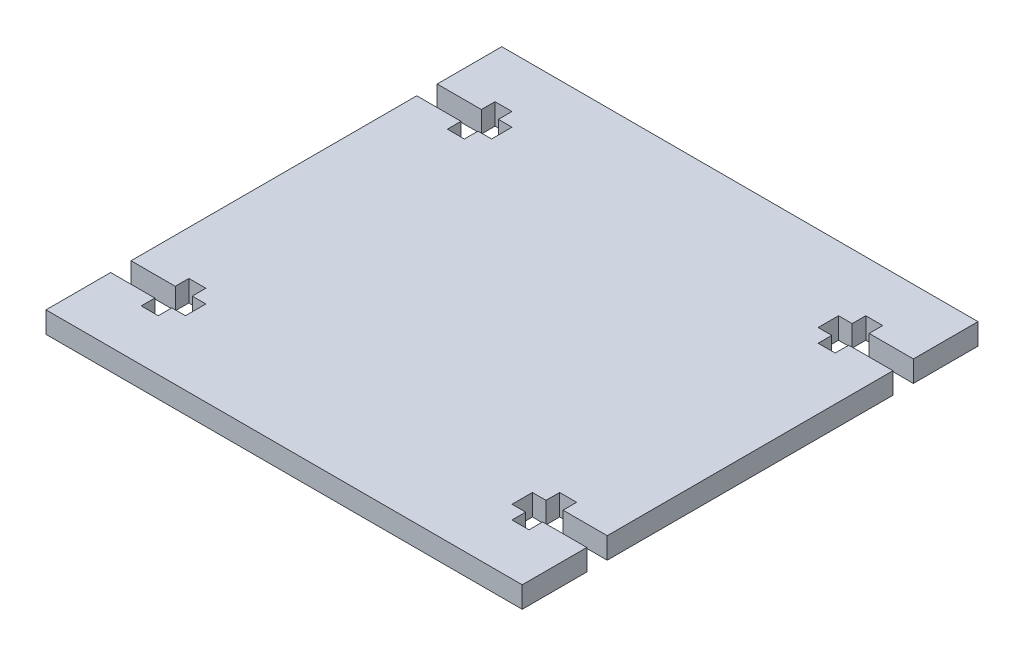
SolidWorks part; units mm, degrees
ref_plane "Front Plane" through (0, 0, 0) normal (0, 0, 1) x (1, 0, 0)
ref_plane "Top Plane" through (0, 0, 0) normal (0, 1, 0) x (1, 0, 0)
ref_plane "Right Plane" through (0, 0, 0) normal (1, 0, 0) x (0, 0, -1)
sketch "Sketch1" plane through (0, 0, 0) normal (0, 1, 0) x (1, 0, 0)
  line L0 (0, 22.5) -> (35, 22.5) construction
  line L1 (0, 33.5) -> (35, 33.5)
  line L2 (0, 33.5) -> (0, 0)
  line L3 (0, 0) -> (35, 0)
  line L4 (35, 33.5) -> (35, 24)
  line L5 (35, 24) -> (28.5, 24)
  line L6 (28.5, 24) -> (28.5, 26)
  line L7 (28.5, 26) -> (26, 26)
  line L8 (26, 26) -> (26, 24)
  line L9 (26, 24) -> (24, 24)
  line L10 (24, 24) -> (24, 21)
  line L11 (24, 21) -> (26, 21)
  line L12 (26, 21) -> (26, 19)
  line L13 (26, 19) -> (28.5, 19)
  line L14 (28.5, 19) -> (28.5, 21)
  line L15 (28.5, 21) -> (35, 21)
  line L16 (35, 21) -> (35, 0)
  point P17 (24, 22.5)
  dimension "D1" = 35
  dimension "D2" = 2.5
  dimension "D3" = 9
  dimension "D4" = 2
  dimension "D5" = 3
  dimension "D6" = 7.5
  dimension "D7" = 7
  dimension "D8" = 22.5
extrude "Boss-Extrude1" add sketch "Sketch1" along normal mid plane 3.125
mirror "Mirror1" about plane through (0, 0, 0) normal (1, 0, 0) of "Boss-Extrude1"
mirror "Mirror4" about plane through (0, 0, 0) normal (0, 0, 1) of "Mirror1"
